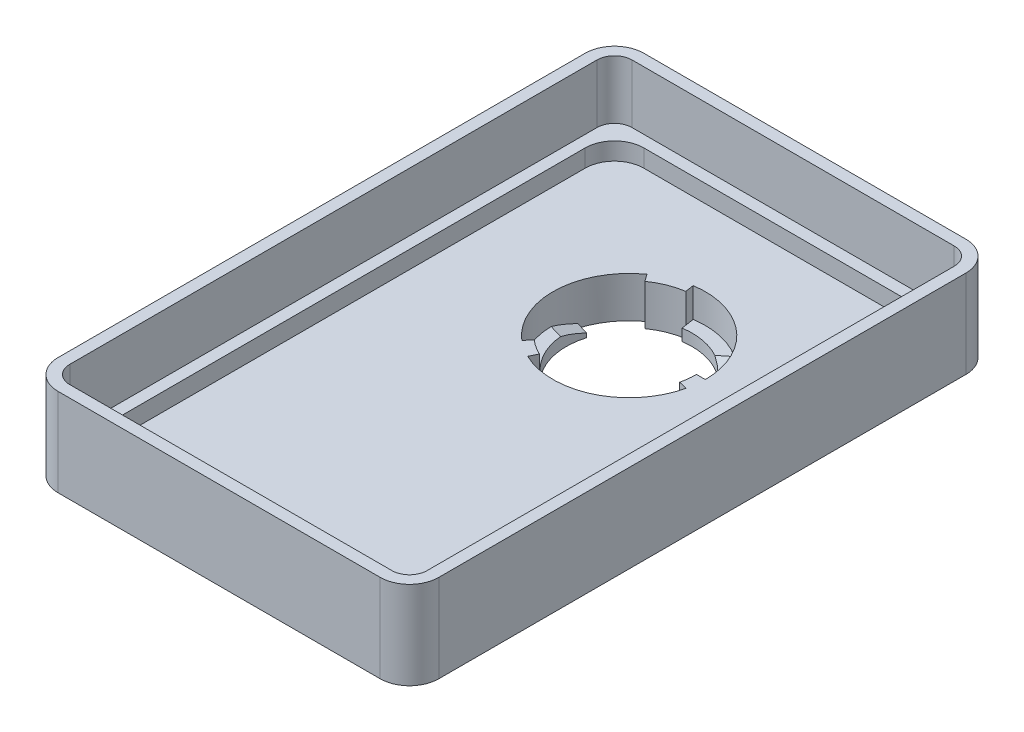
SolidWorks part; units mm, degrees
ref_plane "Front Plane" through (0, 0, 0) normal (0, 0, 1) x (1, 0, 0)
ref_plane "Top Plane" through (0, 0, 0) normal (0, 1, 0) x (1, 0, 0)
ref_plane "Right Plane" through (0, 0, 0) normal (1, 0, 0) x (0, 0, -1)
sketch "Sketch1" plane through (0, 0, 0) normal (0, 1, 0) x (1, 0, 0)
  line L1 (-32.5, 30) -> (32.5, 30)
  line L2 (-32.5, 30) -> (-32.5, -70)
  line L3 (-32.5, -70) -> (32.5, -70)
  line L4 (32.5, 30) -> (32.5, -70)
  line L5 (-32.5, 0) -> (32.5, 0) construction
  point P4 (0, 0)
  dimension "D1" = 65
  dimension "D2" = 100
  dimension "D3" = 30
extrude "Boss-Extrude1" add sketch "Sketch1" along normal blind 2
sketch "Sketch2" plane through (0, 2, 0) normal (0, 1, 0) x (1, 0, 0)
  line L14 (-28.5, -66) -> (28.5, -66)
  line L15 (28.5, -66) -> (28.5, 26)
  line L16 (-28.5, 26) -> (-28.5, -66)
  line L17 (28.5, 26) -> (-28.5, 26)
  line L18 (-28.5, -66) -> (28.5, -66)
  line L19 (28.5, -66) -> (28.5, 26)
  line L20 (-28.5, 26) -> (-28.5, -66)
  line L21 (28.5, 26) -> (-28.5, 26)
  line L32 (-32.5, -70) -> (32.5, -70)
  line L33 (-32.5, 30) -> (-32.5, -70)
  line L34 (32.5, -70) -> (32.5, 30)
  line L35 (32.5, 30) -> (-32.5, 30)
  line L36 (-32.5, -70) -> (32.5, -70)
  line L37 (-32.5, 30) -> (-32.5, -70)
  line L38 (32.5, -70) -> (32.5, 30)
  line L39 (32.5, 30) -> (-32.5, 30)
  dimension "D1" = 4
  dimension "D2" = 0
extrude "Boss-Extrude2" add sketch "Sketch2" along normal blind 3
fillet "Fillet1" radius 5 8 edges at (28.5, 3.5, 66) (-28.5, 3.5, 66) (28.5, 3.5, -26) (-28.5, 3.5, -26) (-32.5, 2.5, 70) (32.5, 2.5, 70) (-32.5, 2.5, -30) (32.5, 2.5, -30)
sketch "Sketch4" plane through (0, 5, 0) normal (0, 1, 0) x (1, 0, 0)
  line L4 (-32.5, 25) -> (-32.5, -65)
  line L5 (-27.5, -70) -> (27.5, -70)
  line L6 (32.5, -65) -> (32.5, 25)
  line L7 (27.5, 30) -> (-27.5, 30)
  line L8 (-30.5, 25) -> (-30.5, -65)
  line L9 (-27.5, -68) -> (27.5, -68)
  line L10 (30.5, -65) -> (30.5, 25)
  line L11 (27.5, 28) -> (-27.5, 28)
  line L12 (-30.5, 25) -> (-30.5, -65)
  line L13 (-27.5, -68) -> (27.5, -68)
  line L14 (30.5, -65) -> (30.5, 25)
  line L15 (27.5, 28) -> (-27.5, 28)
  arc A4 (-32.5, -65) -> (-27.5, -70) centre (-27.5, -65) ccw
  arc A5 (27.5, -70) -> (32.5, -65) centre (27.5, -65) ccw
  arc A6 (32.5, 25) -> (27.5, 30) centre (27.5, 25) ccw
  arc A7 (-27.5, 30) -> (-32.5, 25) centre (-27.5, 25) ccw
  arc A8 (-30.5, -65) -> (-27.5, -68) centre (-27.5, -65) ccw
  arc A9 (27.5, -68) -> (30.5, -65) centre (27.5, -65) ccw
  arc A10 (30.5, 25) -> (27.5, 28) centre (27.5, 25) ccw
  arc A11 (-27.5, 28) -> (-30.5, 25) centre (-27.5, 25) ccw
  arc A12 (-30.5, -65) -> (-27.5, -68) centre (-27.5, -65) ccw
  arc A13 (27.5, -68) -> (30.5, -65) centre (27.5, -65) ccw
  arc A14 (30.5, 25) -> (27.5, 28) centre (27.5, 25) ccw
  arc A15 (-27.5, 28) -> (-30.5, 25) centre (-27.5, 25) ccw
  dimension "D1" = 2
  dimension "D2" = 2
extrude "Boss-Extrude3" add sketch "Sketch4" along normal blind 10
ref_plane "Plane1" through (0, -5, 0) normal (0, -1, 0) x (-1, 0, 0)
sketch "Sketch6" plane through (0, -5, 0) normal (0, -1, 0) x (-1, 0, 0)
  circle A0 centre (0, 0) radius 18
  dimension "D1" = 36
extrude "Boss-Extrude4" add sketch "Sketch6" against normal up to surface (5 mm away) up to face at (0, 0, 20)
chamfer "Chamfer1" distance 10 angle 45 1 edges at (0, 0, 18)
sketch "Sketch7" plane through (0, -5, 0) normal (0, -1, 0) x (1, 0, 0)
  circle A0 centre (0, 0) radius 13
  dimension "D1" = 26
extrude "Cut-Extrude1" cut sketch "Sketch7" against normal through all
sketch "Sketch8" plane through (0, -5, 0) normal (0, -1, 0) x (-1, 0, 0)
  line L0 (0, 0) -> (1.6998, 11.3737)
  line L1 (0, 0) -> (11.0264, 3.2662) construction
  line L2 (0, 0) -> (6.6781, 9.3623) construction
  line L3 (0, 0) -> (1.2021, 11.437) construction
  line L4 (0, 0) -> (12.4647, 3.6922)
  line L5 (0, 0) -> (7.5491, 10.5835)
  line L6 (0, 0) -> (5.5966, -11.7336)
  line L7 (0, 0) -> (-2.4805, -12.7612)
  line L8 (0, 0) -> (-13, 0)
  line L9 (0, 0) -> (-10.1092, 8.1733)
  line L10 (0, 0) -> (8.4428, -9.8853)
  line L11 (0, 0) -> (-12.6668, -2.9244)
  line L12 (1.6998, 11.3737) -> (1.9215, 12.8572)
  circle A0 centre (0, 0) radius 10.75
  circle A1 centre (0, 0) radius 11.5
  circle A2 centre (0, 0) radius 13
  circle A3 centre (0, 0) radius 13 construction
  point P7 (0, 0)
  point P18 (-12.894, 1.6567)
  point P21 (-13, 0)
  point P23 (-12.9543, -1.0891)
  point P24 (0, 0)
  point P25 (-13, 0)
  point P26 (-10.1092, 8.1733)
extrude "Boss-Extrude6" add sketch "Sketch8" against normal blind 2 contours L12 A2 L9 A1 | L5 A2 L12 A1 | L10 A2 L4 A1 | L6 A2 L10 A1 | L0 A1 L9 A0 | L10 A1 L4 A0 | L11 A2 L7 A1 | L11 A1 L7 A0 | L8 A2 L11 A1 region at (3.9424, -5, -10.1261) region at (-10.7033, -5, -3.0366) region at (2.2479, -5, 10.8963) region at (4.2523, -5, -10.9222) region at (-4.5523, -5, -11.2673) region at (-11.1207, -5, 3.2941) region at (-6.6611, -5, 10.2572) region at (8.0569, -5, 8.3431) region at (12.1603, -5, 1.3855)
extrude "Boss-Extrude7" add sketch "Sketch8<5>" against normal up to surface (7 mm away) contours L5 A2 L12 A1 | L6 A2 L10 A1 | L8 A2 L11 A1 region at (-4.5523, -5, -11.2673) region at (-6.6611, -5, 10.2572) region at (12.1603, -5, 1.3855) up to face at (0, 2, 13)
sketch "Sketch8<5>" plane through (0, -5, 0) normal (0, -1, 0) x (-1, 0, 0) same geometry as "Sketch8"
chamfer "Chamfer2" distance 1.3 angle 72 3 edges at (2.2659, -3, 11.6568) (-11.386, -3, -3.3727) (9.2344, -3, -7.466) first distance on face at (2.2659, -4, 11.6568) first distance on face at (-11.386, -4, -3.3727) first distance on face at (9.2344, -4, -7.466)
